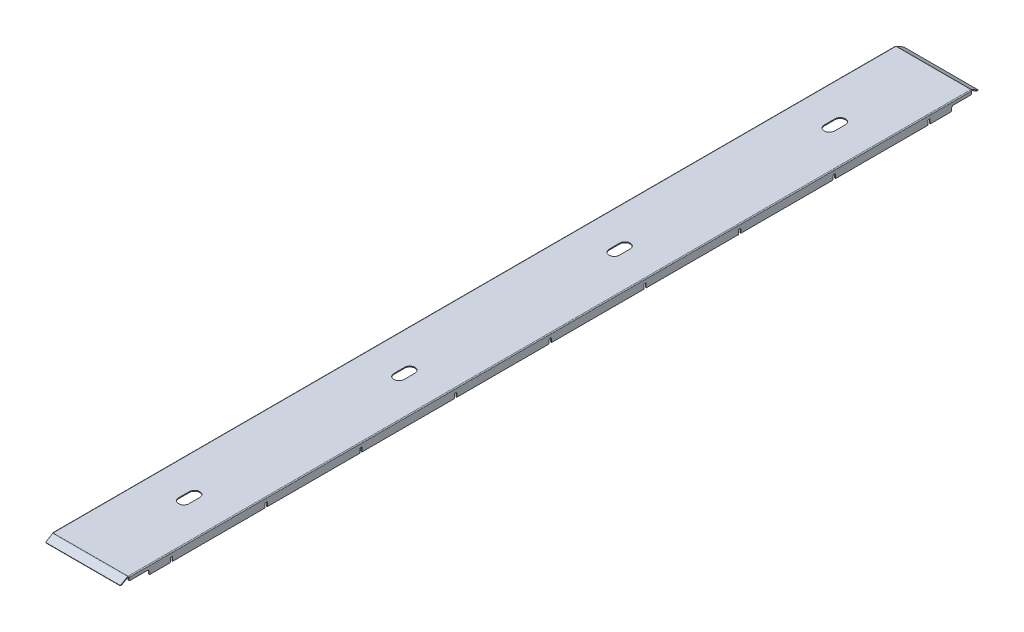
SolidWorks part; units mm, degrees
note: The reader was unsure of these and kept them because the rebuilt part matched: flange length of "Kante-Lasche3", "Kante-Lasche4".
material "1.4301 (X5CrNi18-10)"
ref_plane "Vorne" through (0, 0, 0) normal (0, 0, 1) x (1, 0, 0)
ref_plane "Oben" through (0, 0, 0) normal (0, 1, 0) x (1, 0, 0)
ref_plane "Rechts" through (0, 0, 0) normal (1, 0, 0) x (0, 0, -1)
sketch "Skizze9" plane through (0, 0, 0) normal (0, 1, 0) x (1, 0, 0)
  line L1 (-89, 979) -> (89, 979)
  line L2 (-89, 979) -> (-89, -979)
  line L3 (-89, -979) -> (89, -979)
  line L4 (89, 979) -> (89, -979)
  line L5 (-89, 979) -> (89, -979) construction
  line L6 (-89, -979) -> (89, 979) construction
  point P0 (0, 0)
  dimension "D1" = 1958
  dimension "D2" = 178
sheet metal parameters "Blech3" thickness 2 parameters "D1"=0.01
base flange "Basis-Blech2" sketch "Skizze9" thickness 2 reverse thickness direction no parameters "D1"=0.01
edge flange "Kante-Lasche3" sketch "Skizze61" flange profiles "Skizze61", "Skizze80" flange angle 90 flange length 20 flange position material inside bend radius 0.1 thickness 2 relief rectangular parameters "D6"=10, "D8"=1
sketch "Skizze61" plane through (-89, -2, 0) normal (-1, 0, 0) x (0, 0, -1)
  line L0 (979, 0) -> (-979, 0) construction
  line L1 (979, 0) -> (-979, 0)
  line L2 (-979, 0) -> (-979, 7)
  line L3 (-932, 18) -> (-882.7, 18)
  line L4 (979, 7) -> (979, 0)
  line L5 (-979, 7) -> (-937, 7)
  line L6 (-932, 12) -> (-932, 18)
  line L7 (979, -2) -> (-979, -2) construction
  line L8 (-346.8877, 10) -> (301.2088, 10) construction
  line L9 (-882.7, 10) -> (-882.7, 18)
  line L10 (-877.3, 10) -> (-877.3, 18)
  line L11 (-662.7, 10) -> (-662.7, 18)
  line L12 (-657.3, 10) -> (-657.3, 18)
  line L13 (-442.7, 10) -> (-442.7, 18)
  line L14 (-437.3, 10) -> (-437.3, 18)
  line L15 (-222.7, 10) -> (-222.7, 18)
  line L16 (-217.3, 10) -> (-217.3, 18)
  line L17 (-217.3, 18) -> (-2.7, 18)
  line L18 (-437.3, 18) -> (-222.7, 18)
  line L19 (-657.3, 18) -> (-442.7, 18)
  line L20 (-877.3, 18) -> (-662.7, 18)
  line L21 (0, 128.2129) -> (0, -99.8963) construction
  line L22 (2.7, 10) -> (2.7, 18)
  line L23 (-2.7, 10) -> (-2.7, 18)
  line L24 (2.7, 18) -> (217.3, 18)
  line L25 (217.3, 10) -> (217.3, 18)
  line L26 (222.7, 10) -> (222.7, 18)
  line L27 (437.3, 10) -> (437.3, 18)
  line L28 (442.7, 10) -> (442.7, 18)
  line L29 (657.3, 10) -> (657.3, 18)
  line L30 (662.7, 10) -> (662.7, 18)
  line L31 (877.3, 10) -> (877.3, 18)
  line L32 (882.7, 10) -> (882.7, 18)
  line L33 (932, 12) -> (932, 18)
  line L34 (979, 7) -> (937, 7)
  line L35 (882.7, 18) -> (932, 18)
  line L36 (662.7, 18) -> (877.3, 18)
  line L37 (442.7, 18) -> (657.3, 18)
  line L38 (222.7, 18) -> (437.3, 18)
  arc A0 (-937, 7) -> (-932, 12) centre (-937, 12) ccw
  arc A1 (-882.7, 10) -> (-877.3, 10) centre (-880, 10) ccw
  arc A2 (-662.7, 10) -> (-657.3, 10) centre (-660, 10) ccw
  arc A3 (-442.7, 10) -> (-437.3, 10) centre (-440, 10) ccw
  arc A4 (-222.7, 10) -> (-217.3, 10) centre (-220, 10) ccw
  arc A5 (-2.7, 10) -> (2.7, 10) centre (0, 10) ccw
  arc A6 (222.7, 10) -> (217.3, 10) centre (220, 10) cw
  arc A7 (442.7, 10) -> (437.3, 10) centre (440, 10) cw
  arc A8 (662.7, 10) -> (657.3, 10) centre (660, 10) cw
  arc A9 (882.7, 10) -> (877.3, 10) centre (880, 10) cw
  arc A10 (937, 7) -> (932, 12) centre (937, 12) cw
  dimension "D3" = 5
  dimension "D5" = 2.7
  dimension "D9" = 759
  dimension "D1" = 9
  dimension "D2" = 47
  dimension "D4" = 12
  dimension "D6" = 99
  dimension "D7" = 319
  dimension "D8" = 539
  dimension "D10" = 20
  dimension "D11" = 979
sketch "Skizze80" plane through (89, -2, 0) normal (1, 0, 0) x (0, 0, 1)
  line L0 (979, 0) -> (-979, 0) construction
  line L1 (979, 0) -> (-979, 0)
  line L2 (-979, 0) -> (-979, 7)
  line L3 (979, 7) -> (937, 7) construction
  line L4 (979, 7) -> (979, 0)
  line L5 (932, 12) -> (932, 18) construction
  line L6 (932, 18) -> (882.7, 18) construction
  line L7 (882.7, 10) -> (882.7, 18) construction
  line L8 (877.3, 10) -> (877.3, 18) construction
  line L9 (877.3, 18) -> (662.7, 18) construction
  line L10 (662.7, 10) -> (662.7, 18) construction
  line L11 (657.3, 10) -> (657.3, 18) construction
  line L12 (657.3, 18) -> (442.7, 18) construction
  line L13 (442.7, 10) -> (442.7, 18) construction
  line L14 (437.3, 10) -> (437.3, 18) construction
  line L15 (437.3, 18) -> (222.7, 18) construction
  line L16 (222.7, 10) -> (222.7, 18) construction
  line L17 (217.3, 10) -> (217.3, 18) construction
  line L18 (217.3, 18) -> (2.7, 18) construction
  line L19 (2.7, 10) -> (2.7, 18) construction
  line L20 (-2.7, 10) -> (-2.7, 18) construction
  line L21 (-2.7, 18) -> (-217.3, 18) construction
  line L22 (-217.3, 10) -> (-217.3, 18) construction
  line L23 (-222.7, 10) -> (-222.7, 18) construction
  line L24 (-222.7, 18) -> (-437.3, 18) construction
  line L25 (-437.3, 10) -> (-437.3, 18) construction
  line L26 (-442.7, 10) -> (-442.7, 18) construction
  line L27 (-442.7, 18) -> (-657.3, 18) construction
  line L28 (-657.3, 10) -> (-657.3, 18) construction
  line L29 (-662.7, 10) -> (-662.7, 18) construction
  line L30 (-662.7, 18) -> (-877.3, 18) construction
  line L31 (-877.3, 10) -> (-877.3, 18) construction
  line L32 (-882.7, 10) -> (-882.7, 18) construction
  line L33 (-882.7, 18) -> (-932, 18) construction
  line L34 (-932, 12) -> (-932, 18) construction
  line L35 (-979, 7) -> (-937, 7) construction
  line L36 (979, 7) -> (937, 7)
  line L37 (932, 12) -> (932, 18)
  line L38 (932, 18) -> (882.7, 18)
  line L39 (882.7, 10) -> (882.7, 18)
  line L40 (877.3, 10) -> (877.3, 18)
  line L41 (877.3, 18) -> (662.7, 18)
  line L42 (662.7, 10) -> (662.7, 18)
  line L43 (657.3, 10) -> (657.3, 18)
  line L44 (657.3, 18) -> (442.7, 18)
  line L45 (442.7, 10) -> (442.7, 18)
  line L46 (437.3, 10) -> (437.3, 18)
  line L47 (437.3, 18) -> (222.7, 18)
  line L48 (222.7, 10) -> (222.7, 18)
  line L49 (217.3, 10) -> (217.3, 18)
  line L50 (217.3, 18) -> (2.7, 18)
  line L51 (2.7, 10) -> (2.7, 18)
  line L52 (-2.7, 10) -> (-2.7, 18)
  line L53 (-2.7, 18) -> (-217.3, 18)
  line L54 (-217.3, 10) -> (-217.3, 18)
  line L55 (-222.7, 10) -> (-222.7, 18)
  line L56 (-222.7, 18) -> (-437.3, 18)
  line L57 (-437.3, 10) -> (-437.3, 18)
  line L58 (-442.7, 10) -> (-442.7, 18)
  line L59 (-442.7, 18) -> (-657.3, 18)
  line L60 (-657.3, 10) -> (-657.3, 18)
  line L61 (-662.7, 10) -> (-662.7, 18)
  line L62 (-662.7, 18) -> (-877.3, 18)
  line L63 (-877.3, 10) -> (-877.3, 18)
  line L64 (-882.7, 10) -> (-882.7, 18)
  line L65 (-882.7, 18) -> (-932, 18)
  line L66 (-932, 12) -> (-932, 18)
  line L67 (-979, 7) -> (-937, 7)
  arc A0 (932, 12) -> (937, 7) centre (937, 12) ccw construction
  arc A1 (877.3, 10) -> (882.7, 10) centre (880, 10) ccw construction
  arc A2 (657.3, 10) -> (662.7, 10) centre (660, 10) ccw construction
  arc A3 (437.3, 10) -> (442.7, 10) centre (440, 10) ccw construction
  arc A4 (217.3, 10) -> (222.7, 10) centre (220, 10) ccw construction
  arc A5 (-2.7, 10) -> (2.7, 10) centre (0, 10) ccw construction
  arc A6 (-222.7, 10) -> (-217.3, 10) centre (-220, 10) ccw construction
  arc A7 (-442.7, 10) -> (-437.3, 10) centre (-440, 10) ccw construction
  arc A8 (-662.7, 10) -> (-657.3, 10) centre (-660, 10) ccw construction
  arc A9 (-882.7, 10) -> (-877.3, 10) centre (-880, 10) ccw construction
  arc A10 (-937, 7) -> (-932, 12) centre (-937, 12) ccw construction
  arc A11 (932, 12) -> (937, 7) centre (937, 12) ccw
  arc A12 (877.3, 10) -> (882.7, 10) centre (880, 10) ccw
  arc A13 (657.3, 10) -> (662.7, 10) centre (660, 10) ccw
  arc A14 (437.3, 10) -> (442.7, 10) centre (440, 10) ccw
  arc A15 (217.3, 10) -> (222.7, 10) centre (220, 10) ccw
  arc A16 (-2.7, 10) -> (2.7, 10) centre (0, 10) ccw
  arc A17 (-222.7, 10) -> (-217.3, 10) centre (-220, 10) ccw
  arc A18 (-442.7, 10) -> (-437.3, 10) centre (-440, 10) ccw
  arc A19 (-662.7, 10) -> (-657.3, 10) centre (-660, 10) ccw
  arc A20 (-882.7, 10) -> (-877.3, 10) centre (-880, 10) ccw
  arc A21 (-937, 7) -> (-932, 12) centre (-937, 12) ccw
bend "Kantenbiegung5" bend radius 0.1 bend angle 90 parameters "D5"=9
bend "Kantenbiegung10" bend radius 0.1 bend angle 90 parameters "D5"=14
edge flange "Kante-Lasche4" sketch "Skizze71" flange profiles "Skizze71", "Skizze73" flange angle 150 flange length 20 flange position bend outside bend radius 0.1 thickness 2 relief rectangular parameters "D6"=10, "D8"=1
sketch "Skizze71" plane through (0, -2, 979) normal (0, 0.866, 0.5) x (-1, 0, 0)
  line L0 (86.9, 0) -> (-86.9, 0) construction
  line L1 (86.9, 0) -> (-86.9, 0)
  line L2 (-86.9, 0) -> (-86.9, 19.4641)
  line L3 (-86.9, 19.4641) -> (86.9, 19.4641)
  line L4 (86.9, 19.4641) -> (86.9, 0)
sketch "Skizze73" plane through (0, -2, -979) normal (0, 0.866, -0.5) x (1, 0, 0)
  line L0 (86.9, 0) -> (-86.9, 0) construction
  line L1 (86.9, 0) -> (-86.9, 0)
  line L2 (-86.9, 0) -> (-86.9, 19.4641)
  line L3 (-86.9, 19.4641) -> (86.9, 19.4641)
  line L4 (86.9, 19.4641) -> (86.9, 0)
bend "Kantenbiegung7" bend radius 0.1 bend angle 30 parameters "D5"=11
bend "Kantenbiegung9" bend radius 0.1 bend angle 30 parameters "D5"=13
hole_wizard "M6 Gewindebohrung1" positions "Skizze78" profile "Skizze77" tap size "M6" standard "Gabler-Normteile"
sketch "Skizze78" plane through (-89, 0, 0) normal (-1, 0, 0) x (0, 0, 1)
  arc A0 (662.7, -12) -> (657.3, -12) centre (660, -12) ccw construction
  arc A1 (-437.3, -12) -> (-442.7, -12) centre (-440, -12) ccw construction
  point P0 (-550, -12)
  point P2 (550, -12)
  point P5 (660, -9.3)
  dimension "D1" = 110
  dimension "D2" = 110
sketch "Skizze77" plane through (-89, -12, -550) normal (0, 1, 0) x (0, 0, 1)
  line L0 (0, 0) -> (0, 18.5022)
  line L1 (0, 18.5022) -> (2.5, 17)
  line L2 (2.5, 17) -> (2.5, 0)
  line L5 (2.5, 0) -> (0, 0)
  line L10 (0, 18.5022) -> (-2.5, 17) construction
  line L11 (0, -6.35) -> (0, 107.95) construction
  dimension "Bohrerdurchmesser" = 5
  dimension "Bohrungstiefe" = 17
  dimension "Spitzenwinkel" = 118
cosmetic thread "Bohrungsgewinde1" parameters "D1"=2, "D2"=6
cosmetic thread "Bohrungsgewinde2" parameters "D1"=2, "D2"=6
sketch "Skizze81" plane through (0, 0, 0) normal (0, 1, 0) x (1, 0, 0)
  line L0 (0, -737.5) -> (0, -762.5) construction
  line L1 (12, -737.5) -> (12, -762.5)
  line L2 (-12, -737.5) -> (-12, -762.5)
  line L3 (0, -237.5) -> (0, -262.5) construction
  line L4 (12, -237.5) -> (12, -262.5)
  line L5 (-12, -237.5) -> (-12, -262.5)
  line L6 (0, 262.5) -> (0, 237.5) construction
  line L7 (12, 262.5) -> (12, 237.5)
  line L8 (-12, 262.5) -> (-12, 237.5)
  line L9 (0, 762.5) -> (0, 737.5) construction
  line L10 (12, 762.5) -> (12, 737.5)
  line L11 (-12, 762.5) -> (-12, 737.5)
  arc A0 (12, -737.5) -> (-12, -737.5) centre (0, -737.5) ccw
  arc A1 (-12, -762.5) -> (12, -762.5) centre (0, -762.5) ccw
  arc A2 (12, -237.5) -> (-12, -237.5) centre (0, -237.5) ccw
  arc A3 (-12, -262.5) -> (12, -262.5) centre (0, -262.5) ccw
  arc A4 (12, 262.5) -> (-12, 262.5) centre (0, 262.5) ccw
  arc A5 (-12, 237.5) -> (12, 237.5) centre (0, 237.5) ccw
  arc A6 (12, 762.5) -> (-12, 762.5) centre (0, 762.5) ccw
  arc A7 (-12, 737.5) -> (12, 737.5) centre (0, 737.5) ccw
  point P3 (0, -750)
  point P11 (0, -250)
  point P18 (0, 250)
  point P25 (0, 750)
  dimension "D5" = 12
  dimension "D2" = 500
  dimension "D3" = 250
  dimension "D4" = 500
  dimension "D6" = 25
  dimension "D1" = 4
extrude "Schnitt-Linear austragen1" cut sketch "Skizze81" against normal blind 10 normal cut yes
fillet "Verrundung1" radius 2 12 edges at (88, -20, -932) (88, -9, -979) (86.9, -10.866, -996.3832) (-86.9, -10.866, -996.3832) (-88, -9, -979) (-88, -20, -932) (-88, -20, 932) (-88, -9, 979) (-86.9, -10.866, 996.3832) (88, -20, 932) (88, -9, 979) (86.9, -10.866, 996.3832)
flat pattern "Abwicklung3" [suppressed]
sketch "Biegung-Linien3" plane through (0, -2, 0) normal (0, -1, 0) x (1, 0, 0)
  line L1 (72.5, -979.2644) -> (-70.49, -979.2644) construction
  line L2 (-70.49, 979.2644) -> (72.5, 979.2644) construction
  line L3 (-71.2833, -979) -> (-71.2833, 979) construction
  line L5 (72.5, -979.2644) -> (-70.49, -979.2644) construction
  line L6 (-70.49, 979.2644) -> (72.5, 979.2644) construction
  line L7 (-71.2833, -979) -> (-71.2833, 979) construction
sketch3d "Rahmen3" [suppressed]
  line L0 (-162.5665, -1977.9903, 0) -> (-162.5665, 19.9903, 0) construction
  line L1 (8.4018, -1977.9903, 0) -> (8.4018, 19.9903, 0) construction
  line L2 (-162.5665, -1977.9903, 0) -> (8.4018, -1977.9903, 0) construction
  line L3 (-162.5665, 19.9903, 0) -> (8.4018, 19.9903, 0) construction
bend of the flat pattern "Abwickeln-<Kantenbiegung5>1"
bend of the flat pattern "Abwickeln-<Kantenbiegung7>1"
bend of the flat pattern "Abwickeln-<Kantenbiegung9>1"
bend of the flat pattern "Abwickeln-<Kantenbiegung10>1"
